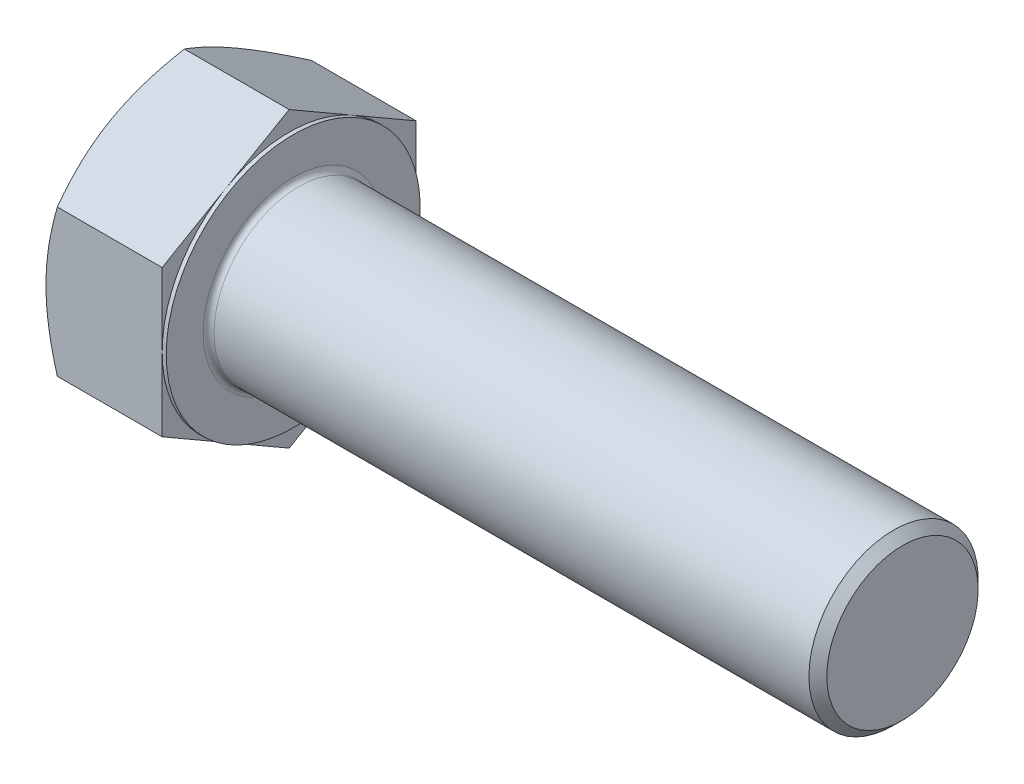
SolidWorks part; units mm, degrees
extrude "BaseHead" add sketch "Sketch1" along normal blind 11.2776
sketch "Sketch1" plane through (0, 0, 0) normal (1, 0, 0) x (0, 0, -1)
  line L0 (11.9126, 6.8777) -> (11.9126, -6.8777)
  line L1 (-11.9126, 6.8777) -> (-11.9126, -6.8777)
  line L2 (11.9126, -6.8777) -> (0, -13.7555)
  line L3 (0, -13.7555) -> (-11.9126, -6.8777)
  line L4 (11.9126, 6.8777) -> (0, 13.7555)
  line L5 (0, 13.7555) -> (-11.9126, 6.8777)
  dimension "D2" = 120
  dimension "D3" = 11.9126
  dimension "D4" = 11.9126
  dimension "D5" = 11.9126
revolve "HeadChamfer" cut sketch "Sketch3" angle 360 about L6 other way angle 60
sketch "Sketch3" plane through (0, 0, 0) normal (0, 0, 1) x (1, 0, 0)
  line L0 (0, 11.9126) -> (4.7302, 20.1055)
  line L1 (0, 13.7555) -> (0, 6.8777) construction
  line L2 (4.7302, 20.1055) -> (4.7302, 26.4555)
  line L3 (4.7302, 26.4555) -> (-12.7, 26.4555)
  line L4 (-12.7, 26.4555) -> (-12.7, 11.9126)
  line L5 (-12.7, 11.9126) -> (0, 11.9126)
  line L6 (0, 0) -> (99.06, 0) construction
  line L7 (11.2776, 13.7555) -> (0, 13.7555) construction
  dimension "D1" = 11.9126
  dimension "D2" = 6.35
  dimension "D3" = 12.7
  dimension "D4" = 6.35
  dimension "Head_ch_ang" = 30
ref_plane "Plane1" through (0, 0, 0) normal (0, 0, 1) x (1, 0, 0)
ref_plane "Plane2" through (0, 0, 0) normal (0, 1, 0) x (1, 0, 0)
ref_plane "Plane3" through (0, 0, 0) normal (1, 0, 0) x (0, 0, -1)
sketch "BodySke" plane through (0, 0, 0) normal (0, 0, 1) x (1, 0, 0)
  line L0 (0, 6.8777) -> (0, -6.8777) construction
  line L1 (0, 0) -> (68.4276, 0)
  line L2 (0, 0) -> (0, 7.9375)
  line L3 (0, 7.9375) -> (67.5881, 7.9375)
  line L4 (68.4276, 0) -> (68.4276, 7.098)
  line L5 (11.2776, 13.7555) -> (11.2776, 6.8777) construction
  line L6 (68.4276, 7.098) -> (67.5881, 7.9375)
  line L7 (0, 0) -> (96.52, 0) construction
  line L8 (68.4276, -7.098) -> (67.5881, -7.9375) construction
  line L9 (0, -7.9375) -> (67.5881, -7.9375) construction
  line L10 (12.6873, 15.24) -> (12.6873, -1.27) construction
  line L11 (11.2776, 15.24) -> (11.2776, -1.27) construction
  line L12 (11.2776, 6.8777) -> (11.2776, -6.8777) construction
  dimension "Diameter" = 15.875
revolve "BaseBody" add sketch "BodySke" angle 360 about L7
cosmetic thread "ThreadCosmetic" [suppressed] parameters "Thread_length"=55.7403, "Thread_minor"=14.1961
sketch "Sketch4" plane through (0, 0, 0) normal (0, 0, 1) x (1, 0, 0)
  line L1 (11.2776, 13.7555) -> (11.2776, 6.8777) construction
  line L2 (11.2776, 11.9126) -> (10.8966, 11.9126)
  line L3 (11.2776, 11.9126) -> (11.2776, 39.1555)
  line L4 (11.2776, 39.1555) -> (10.8966, 39.1555)
  line L5 (0, 0) -> (95.25, 0) construction
  line L6 (0, 0) -> (96.52, 0) construction
  line L7 (10.8966, 11.9126) -> (10.8966, 39.1555)
  line L8 (11.2776, 13.7555) -> (1.064, 13.7555) construction
  dimension "D1" = 11.9126
  dimension "D2" = 25.4
revolve "BearingFace" cut sketch "Sketch4" angle 360 about L5
fillet "HeadFillet" radius 0.508 1 edges at (11.2776, 0, -7.9375)
sketch "ThdSchSke" plane through (0, 0, 0) normal (0, 0, 1) x (1, 0, 0)
  line L0 (12.6873, -7.098) -> (12.0995, -7.9375)
  line L1 (12.6873, -7.098) -> (13.2751, -7.9375)
  line L2 (13.2751, -7.9375) -> (13.2751, -9.9219)
  line L3 (-3.175, 0) -> (5.1513, 0) construction
  line L5 (13.2751, -9.9219) -> (12.0995, -9.9219)
  line L6 (12.0995, -9.9219) -> (12.0995, -7.9375)
  dimension "Thread_minor" = 14.1961
  dimension "Diameter" = 15.875
  dimension "Start" = 12.6873
revolve "ThreadSchematic" [suppressed] cut sketch "ThdSchSke" angle 360 about L3
pattern_linear "ThdSchPat" [suppressed]
equation "\"D3@Sketch1\" = \"Width_flats@Sketch1\" / 2"
equation "\"D4@Sketch1\" = \"D3@Sketch1\""
equation "\"D5@Sketch1\" = \"D4@Sketch1\""
equation "\"Thread_minor@ThreadCosmetic\" = \"Minor_dia@BodySke\""
equation "\"D1@Sketch3\" = \"Width_flats@Sketch1\" / 2"
equation "\"D1@Sketch4\"= \"Width_flats@Sketch1\" / 2"
equation "\"Thread_length@ThreadCosmetic\"= ((sgn( (\"Length@BodySke\" - \"Advance@BodySke\" ) - \"Thread_nom@BodySke\" )-1)*( (\"Length@BodySke\" - \"Advance@BodySke\" ) - \"Thread_nom@BodySke\" ))/-2+ \"Thread_nom@BodySke\""
equation "\"Thread_minor@ThdSchSke\"= \"Minor_dia@BodySke\""
equation "\"Diameter@ThdSchSke\" = \"Diameter@BodySke\""
equation "\"Overcut@ThdSchSke\" = \"Diameter@BodySke\" * 1.25"
equation "\"Start@ThdSchSke\" = \"Head_ht@BaseHead\" + \"Length@BodySke\" - \"Thread_length@ThreadCosmetic\"  '---Non-countersunk---"
equation "\"Num_threads@ThdSchPat\" = int( \"Thread_length@ThreadCosmetic\" / \"Advance@BodySke\" + 0.999 )  + 1"
equation "\"Advance@ThdSchPat\" = \"Thread_length@ThreadCosmetic\" /  (\"Num_threads@ThdSchPat\" - 1) 'relax it"
equation "\"Num_threads@ThdSchPat\" = \"Num_threads@ThdSchPat\" - sgn( \"Num_threads@ThdSchPat\" - 1) '---chamfered tips only---"
